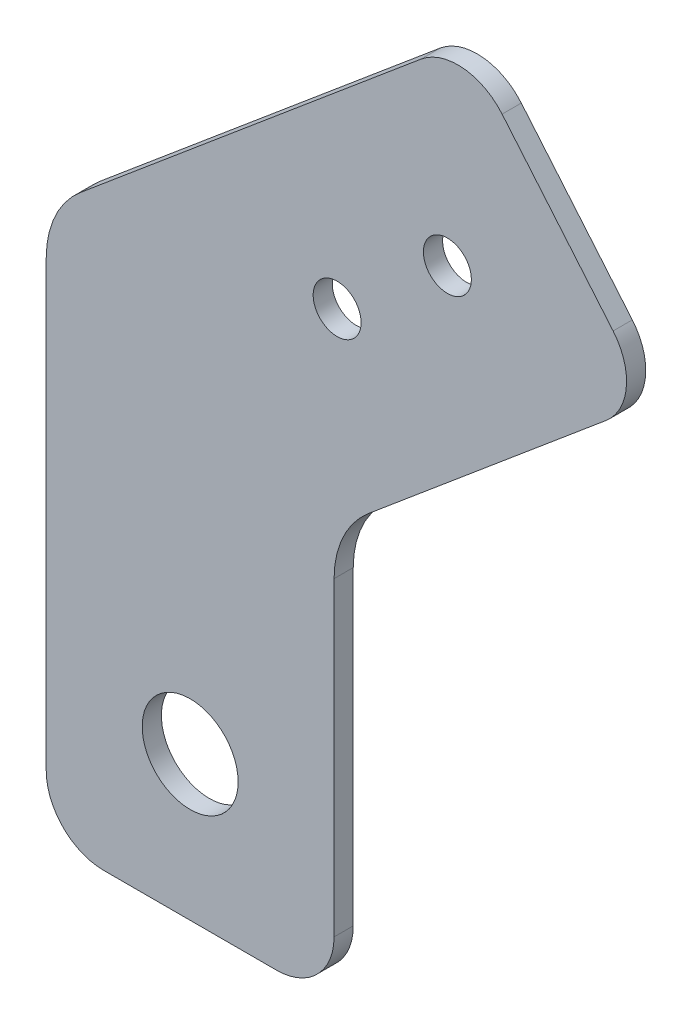
SolidWorks part; units mm, degrees
note: The reader was unsure of these and kept them because the rebuilt part matched: thickness of "Base-Flange1", "Sheet-Metal1".
material "Plain Carbon Steel"
ref_plane "Front Plane" through (0, 0, 0) normal (0, 0, 1) x (1, 0, 0)
ref_plane "Top Plane" through (0, 0, 0) normal (0, 1, 0) x (1, 0, 0)
ref_plane "Right Plane" through (0, 0, 0) normal (1, 0, 0) x (0, 0, -1)
sketch "Sketch1" plane through (0, 0, 0) normal (0, 0, 1) x (1, 0, 0)
  line L0 (0, 0) -> (0, -28.3801) construction
  line L1 (0, 0) -> (-38.3022, -32.1394) construction
  line L2 (-38.3022, -32.1394) -> (-38.3022, -67.1394) construction
  line L3 (-14.2381, 7.6339) -> (-49.7301, -22.1474)
  line L4 (-53.3022, -29.8078) -> (-53.3022, -48.5616)
  line L5 (5.0455, -15.3474) -> (-19.7301, -36.1366)
  line L6 (-23.3022, -43.7971) -> (-23.3022, -48.5616)
  line L7 (5.7851, -6.8944) -> (-5.7851, 6.8944)
  line L8 (-53.3022, -25.1448) -> (-53.3022, -67.1394) construction
  line L9 (-23.3022, -39.134) -> (-23.3022, -67.1394) construction
  line L10 (-9.6418, 11.4907) -> (-53.3022, -25.1448) construction
  line L11 (9.6418, -11.4907) -> (-23.3022, -39.134) construction
  line L13 (-23.3022, -48.5616) -> (-23.3022, -76.1394)
  line L14 (-29.3022, -82.1394) -> (-47.3022, -82.1394)
  line L15 (-53.3022, -76.1394) -> (-53.3022, -48.5616)
  circle A1 centre (-38.3022, -67.1394) radius 5
  arc A4 (-49.7301, -22.1474) -> (-53.3022, -29.8078) centre (-43.3022, -29.8078) ccw
  arc A5 (-19.7301, -36.1366) -> (-23.3022, -43.7971) centre (-13.3022, -43.7971) ccw
  circle A6 centre (-11.4907, -9.6418) radius 2.5
  circle A7 centre (-22.9813, -19.2836) radius 2.5
  arc A11 (-47.3022, -82.1394) -> (-53.3022, -76.1394) centre (-47.3022, -76.1394) cw
  arc A12 (-23.3022, -76.1394) -> (-29.3022, -82.1394) centre (-29.3022, -76.1394) cw
  arc A13 (5.0455, -15.3474) -> (5.7851, -6.8944) centre (1.1888, -10.7511) ccw
  arc A14 (-14.2381, 7.6339) -> (-5.7851, 6.8944) centre (-10.3814, 3.0377) cw
  dimension "D7" = 2
  dimension "D6" = 6
  dimension "D4" = 15
  dimension "D8" = 10
  dimension "D1" = 50
  dimension "D5" = 130
  dimension "D9" = 30
  dimension "D10" = 15
  dimension "D11" = 50
  dimension "32" = 35
  dimension "D2" = 15
  dimension "D3" = 15
base flange "Base-Flange1" sketch "Sketch1" thickness 2 reverse thickness direction no parameters "D1"=0.7366
sketch "Sketch10" [suppressed] plane through (0, 0, -3) normal (0, 0, -1) x (-1, 0, 0)
  line L0 (28.4978, -44.7167) -> (58.4978, -30.7274)
  line L2 (55.8626, -27.2932) -> (9.6418, 11.4907)
  line L3 (9.6418, 11.4907) -> (-9.6418, -11.4907)
  line L4 (-9.6418, -11.4907) -> (25.8626, -41.2824)
  arc A0 (29.4347, -48.9428) -> (25.8626, -41.2824) centre (19.4347, -48.9428) ccw construction
  arc A1 (59.4347, -34.9536) -> (55.8626, -27.2932) centre (49.4347, -34.9536) ccw construction
  arc A2 (25.8626, -41.2824) -> (28.4978, -44.7167) centre (19.4347, -48.9428) cw
  arc A3 (55.8626, -27.2932) -> (58.4978, -30.7274) centre (49.4347, -34.9536) cw
  circle A4 centre (11.4907, -9.6418) radius 2.5
  circle A5 centre (22.9813, -19.2836) radius 2.5
  circle A6 centre (34.472, -28.9254) radius 2.5
sketch "Bend-Lines1" [suppressed] plane through (0, 0, 0) normal (0, 1, 0) x (1, 0, 0)
sketch "Bounding-Box1" [suppressed] plane through (0, 0, 0) normal (0, 1, 0) x (1, 0, 0)
sheet metal parameters "Sheet-Metal1" thickness 2 parameters "D1"=0.7366
flat pattern "Flat-Pattern1" [suppressed]
sketch "Bend-Lines2" plane through (0, 0, 0) normal (0, 0, 1) x (1, 0, 0)
sketch3d "Bounding-Box2" [suppressed]
  line L0 (17.6872, -14.8679, 0) -> (59.6795, 75.1848, 0) construction
  line L1 (-26.0591, 5.5313, 0) -> (15.9331, 95.584, 0) construction
  line L2 (17.6872, -14.8679, 0) -> (-26.0591, 5.5313, 0) construction
  line L3 (59.6795, 75.1848, 0) -> (15.9331, 95.584, 0) construction
sketch "Sketch10-2" [suppressed] plane through (0, 0, -3) normal (0, 0, -1) x (-1, 0, 0)
  line L0 (28.4978, -44.7167) -> (58.4978, -30.7274)
  line L2 (55.8626, -27.2932) -> (9.6418, 11.4907)
  line L3 (9.6418, 11.4907) -> (-9.6418, -11.4907)
  line L4 (-9.6418, -11.4907) -> (25.8626, -41.2824)
  arc A2 (25.8626, -41.2824) -> (28.4978, -44.7167) centre (19.4347, -48.9428) cw
  arc A3 (55.8626, -27.2932) -> (58.4978, -30.7274) centre (49.4347, -34.9536) cw
  circle A4 centre (11.4907, -9.6418) radius 2.5
  circle A5 centre (22.9813, -19.2836) radius 2.5
  circle A6 centre (34.472, -28.9254) radius 2.5
